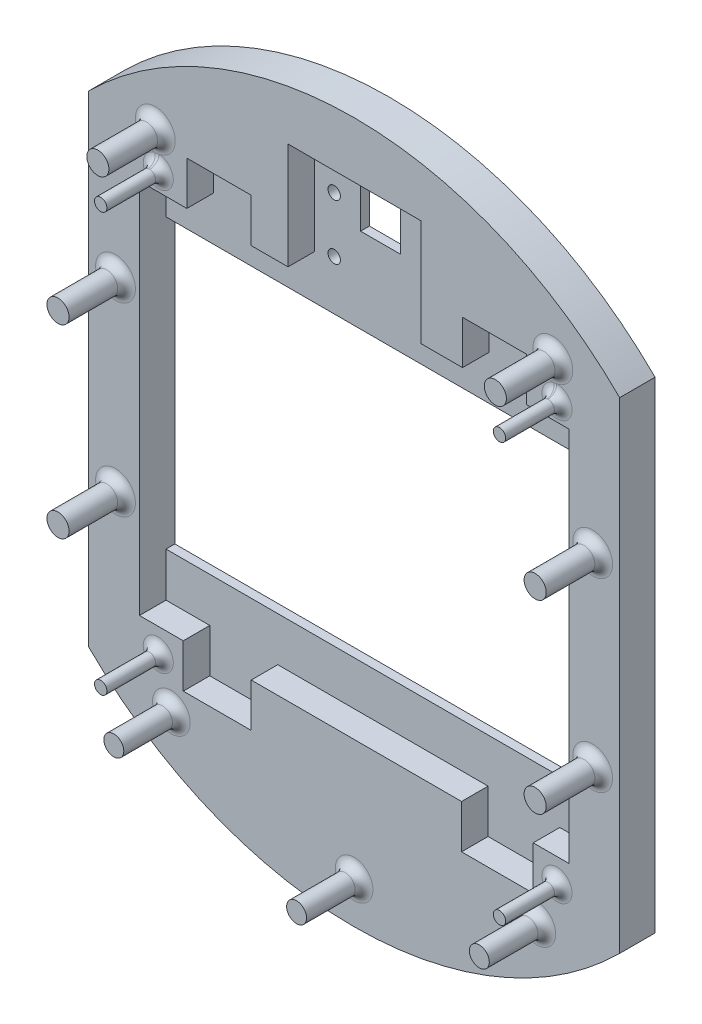
SolidWorks part; units mm, degrees
material "ABS"
ref_plane "Plano frontal" through (0, 0, 0) normal (0, 0, 1) x (1, 0, 0)
ref_plane "Plano superior" through (0, 0, 0) normal (0, 1, 0) x (1, 0, 0)
ref_plane "Plano direito" through (0, 0, 0) normal (1, 0, 0) x (0, 0, -1)
sketch "Esboço1" plane through (0, 0, 0) normal (0, 0, 1) x (1, 0, 0)
  line L0 (0, 0) -> (0, -108.75)
  line L1 (120, -108.75) -> (120, 0)
  line L2 (60, -11.4098) -> (60, -97.3402) construction
  line L3 (120, -54.375) -> (-37.4329, -54.375) construction
  line L4 (11.5, -86.875) -> (108.5, -86.875)
  line L5 (11.5, -86.875) -> (11.5, -21.875)
  line L6 (11.5, -21.875) -> (108.5, -21.875)
  line L7 (108.5, -86.875) -> (108.5, -21.875)
  line L8 (11.5, -86.875) -> (108.5, -21.875) construction
  line L9 (11.5, -21.875) -> (108.5, -86.875) construction
  arc A4 (0, 0) -> (120, 0) centre (60, -60.208) cw
  arc A5 (0, -108.75) -> (120, -108.75) centre (60, -48.542) ccw
  point P9 (60, -54.375)
  point P17 (60, 24.792)
  dimension "D1" = 108.75
  dimension "D5" = 85
  dimension "D2" = 65
  dimension "D3" = 97
extrude "Ressalto-extrusão1" add sketch "Esboço1" along normal blind 8
sketch "Esboço2" plane through (0, 0, 8) normal (0, 0, 1) x (1, 0, 0)
  line L0 (11.5, -54.375) -> (108.5, -54.375) construction
  line L1 (11.5, -21.875) -> (11.5, -86.875) construction
  line L2 (108.5, -86.875) -> (108.5, -21.875) construction
  line L3 (108.5, -21.875) -> (11.5, -21.875) construction
  line L4 (11.5, -96.875) -> (108.5, -96.875)
  line L5 (11.5, -96.875) -> (11.5, -11.875)
  line L6 (11.5, -11.875) -> (108.5, -11.875)
  line L7 (108.5, -96.875) -> (108.5, -11.875)
  line L8 (11.5, -96.875) -> (108.5, -11.875) construction
  line L9 (11.5, -11.875) -> (108.5, -96.875) construction
  point P6 (60, -54.375)
  dimension "D1" = 10
extrude "Corte-extrusão1" cut sketch "Esboço2" against normal blind 6
sketch "Esboço3" plane through (0, 0, 8) normal (0, 0, 1) x (1, 0, 0)
  line L0 (-24.8022, -47.1436) -> (153.0643, -47.1436) construction
  line L1 (113.9062, -94.6477) -> (113.9062, -101.6218) construction
  line L2 (6.0938, 0) -> (113.9062, 0) construction
  line L3 (60, 24.792) -> (60, -133.542) construction
  line L5 (0, 0) -> (0, -108.75) construction
  line L6 (0, -12.5) -> (6.0938, -12.5) construction
  line L7 (6.0938, -12.5) -> (6.0938, -102.188) construction
  line L8 (35.13, -11.875) -> (35.13, -106.875) construction
  line L9 (108.5, -11.875) -> (11.5, -11.875) construction
  line L10 (60, -133.542) -> (60, -106.875)
  arc A0 (6.0938, -102.188) -> (113.9062, -102.188) centre (60, -47.1436) ccw
  circle A1 centre (18.7084, -112.188) radius 2.25
  circle A2 centre (60, -124.1876) radius 2.25
  circle A3 centre (101.2916, -112.188) radius 2.25
  circle A4 centre (104.9062, 0) radius 2.5
  circle A6 centre (15.0938, 0) radius 2.5
  arc A7 (120, 0) -> (0, 0) centre (60, -60.208) ccw construction
  arc A8 (0, -108.75) -> (120, -108.75) centre (60, -48.542) ccw construction
  circle A9 centre (6.0938, -75.315) radius 2.5
  circle A10 centre (6.0938, -33.44) radius 2.5
  circle A11 centre (113.9062, -75.315) radius 2.5
  circle A12 centre (113.9062, -33.44) radius 2.5
  point P2 (15.1324, 0)
  point P6 (103.9729, 0)
  point P17 (0, 0)
  point P39 (60, -11.875)
  dimension "D1" = 4.5
  dimension "D2" = 5
  dimension "D7" = 77.044
  dimension "D3" = 41.875
  dimension "D4" = 20.94
  dimension "D5" = 10
  dimension "D6" = 89.688
  dimension "D8" = 41.2916
  dimension "D9" = 26.667
  dimension "D10" = 36.667
  dimension "D11" = 9.3545
  dimension "D12" = 107.8125
  dimension "D13" = 9
  dimension "D14" = 9
extrude "Ressalto-extrusão2" add sketch "Esboço3" along normal blind 13 contours A9 | A1 | A2 | A3 | A11 | A12 | A4 | A6 | A10
fillet "Filete1" radius 2 9 edges at (12.5938, 0, 8) (3.5937, -33.44, 8) (3.5937, -75.315, 8) (16.4584, -112.188, 8) (57.75, -124.1876, 8) (99.0416, -112.188, 8) (111.4062, -75.315, 8) (111.4063, -33.44, 8) (102.4062, 0, 8)
sketch "Esboço5" plane through (0, 0, 8) normal (0, 0, 1) x (1, 0, 0)
  line L0 (47.0593, -11.875) -> (47.0593, 1.21)
  line L1 (108.5, -11.875) -> (11.5, -11.875) construction
  line L2 (47.0593, 1.21) -> (73.076, 1.21)
  line L3 (73.076, 1.21) -> (73.076, -25.3836)
  line L4 (73.076, -25.3836) -> (47.0593, -25.3836)
  line L5 (47.0593, -25.3836) -> (47.0593, -11.875)
extrude "Corte-extrusão3" cut sketch "Esboço5" against normal blind 5
sketch "Esboço6" plane through (0, 0, 8) normal (0, 0, 1) x (1, 0, 0)
  line L0 (60, 24.792) -> (60, -141.3459) construction
  line L1 (0, -54.375) -> (135.5539, -54.375) construction
  line L2 (0, 0) -> (0, -108.75) construction
  circle A0 centre (15.75, -7.815) radius 1.4
  arc A1 (120, 0) -> (0, 0) centre (60, -60.208) ccw construction
  circle A5 centre (105.85, -102.335) radius 1.4
  circle A6 centre (15.75, -102.335) radius 1.4
  circle A7 centre (105.85, -7.815) radius 1.4
  dimension "D1" = 2.8
extrude "Ressalto-extrusão3" add sketch "Esboço6" along normal up to surface (13 mm away) up to face at (111.4062, -75.315, 21)
fillet "Filete2" radius 2 4 edges at (104.45, -7.815, 8) (14.35, -102.335, 8) (104.45, -102.335, 8) (14.35, -7.815, 8)
sketch "Esboço8" plane through (0, 0, 8) normal (0, 0, 1) x (1, 0, 0)
  line L0 (45.0677, 1.21) -> (45.0677, 12.1682)
  line L1 (45.0677, 12.1682) -> (75.0677, 12.1682)
  line L2 (75.0677, 12.1682) -> (75.0677, -15.935)
  line L3 (75.0677, -15.935) -> (45.0677, -15.935)
  line L4 (45.0677, -15.935) -> (45.0677, 1.21)
  line L5 (73.076, 1.21) -> (47.0593, 1.21) construction
  point P8 (60.0677, -15.935)
  point P11 (60.0677, 1.21)
  dimension "D1" = 30
extrude "Corte-extrusão5" cut sketch "Esboço8" against normal up to surface (6 mm away) up to face at (60, -16.875, 2)
sketch "Esboço9" plane through (0, 0, 2) normal (0, 0, 1) x (1, 0, 0)
  line L1 (55.4685, 6.3063) -> (64.4685, 6.3063)
  line L2 (55.4685, 6.3063) -> (55.4685, -2.6937)
  line L3 (55.4685, -2.6937) -> (64.4685, -2.6937)
  line L4 (64.4685, 6.3063) -> (64.4685, -2.6937)
  line L5 (55.4685, 6.3063) -> (64.4685, -2.6937) construction
  line L6 (55.4685, -2.6937) -> (64.4685, 6.3063) construction
  circle A0 centre (49.5, -10.635) radius 1.4
  circle A1 centre (49.5, 1.865) radius 1.4
  circle A2 centre (70.5, 1.865) radius 1.4
  circle A3 centre (70.5, -10.635) radius 1.4
  point P12 (59.9685, 1.8063)
  dimension "D3" = 2.8
  dimension "D1" = 9
  dimension "D2" = 9
extrude "Corte-extrusão6" cut sketch "Esboço9" against normal through all
sketch "Esboço10" plane through (0, 0, 8) normal (0, 0, 1) x (1, 0, 0)
  line L0 (21.3948, -96.875) -> (21.3948, -106.7323)
  line L1 (11.5, -96.875) -> (108.5, -96.875) construction
  line L2 (21.3948, -106.7323) -> (36.7519, -106.7323)
  line L3 (36.7519, -106.7323) -> (36.7519, -95.2323)
  line L4 (36.7519, -95.2323) -> (21.3948, -95.2323)
  line L5 (21.3948, -95.2323) -> (21.3948, -96.875)
  line L6 (60, 24.792) -> (60, -137.3046) construction
  line L7 (0, -54.375) -> (133.7853, -54.375) construction
  line L8 (0, 0) -> (0, -108.75) construction
  line L9 (100.4681, -95.2347) -> (100.4681, -96.875)
  line L10 (84.2738, -95.2347) -> (100.4681, -95.2347)
  line L11 (84.2738, -106.7347) -> (84.2738, -95.2347)
  line L12 (100.4681, -106.7347) -> (84.2738, -106.7347)
  line L13 (100.4681, -96.875) -> (100.4681, -106.7347)
  line L14 (98.9669, -12.0402) -> (98.9669, -2.0177)
  line L15 (98.9669, -2.0177) -> (84.4999, -2.0177)
  line L16 (84.4999, -2.0177) -> (84.4999, -13.5177)
  line L17 (84.4999, -13.5177) -> (98.9669, -13.5177)
  line L18 (98.9669, -13.5177) -> (98.9669, -12.0402)
  line L19 (22.2093, -13.5177) -> (22.2093, -11.875)
  line L20 (36.7519, -13.5177) -> (22.2093, -13.5177)
  line L21 (36.7519, -2.0177) -> (36.7519, -13.5177)
  line L22 (22.2093, -2.0177) -> (36.7519, -2.0177)
  line L23 (22.2093, -11.875) -> (22.2093, -2.0177)
  arc A0 (120, 0) -> (0, 0) centre (60, -60.208) ccw construction
  point P32 (100.4681, -95.2323)
  point P33 (100.4681, -96.875)
  dimension "D2" = 11.5
extrude "Corte-extrusão7" cut sketch "Esboço10" against normal up to surface (6 mm away) up to face at (50.9, 1.865, 2)
